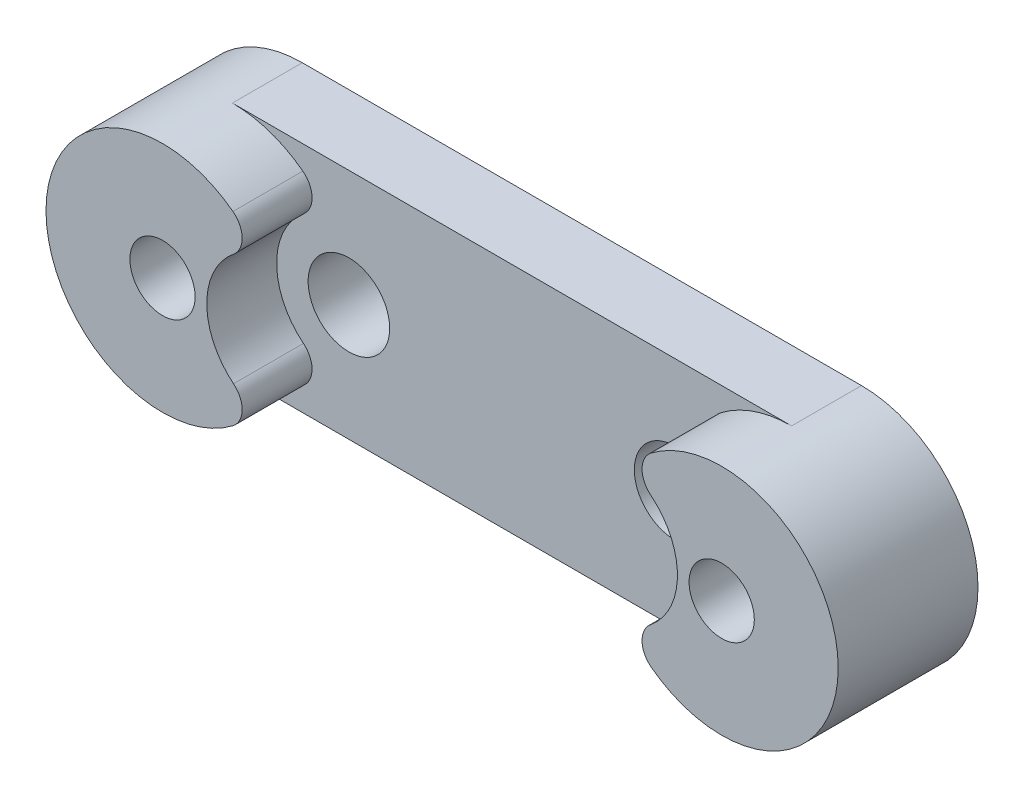
SolidWorks part; units mm, degrees
ref_plane "Front Plane" through (0, 0, 0) normal (0, 0, 1) x (1, 0, 0)
ref_plane "Top Plane" through (0, 0, 0) normal (0, 1, 0) x (1, 0, 0)
ref_plane "Right Plane" through (0, 0, 0) normal (1, 0, 0) x (0, 0, -1)
sketch "Sketch1" plane through (0, 0, 0) normal (0, 0, 1) x (1, 0, 0)
  line L0 (0, 19.1439) -> (0, 0) construction
  line L1 (0, 0) -> (-7, 0) construction
  line L2 (-12, 0) -> (12, 0) construction
  line L3 (-12, 5) -> (12, 5)
  line L4 (-12, -5) -> (12, -5)
  circle A0 centre (-7, 0) radius 1.75
  circle A1 centre (-12, 0) radius 1.75
  circle A2 centre (12, 0) radius 1.75
  circle A3 centre (7, 0) radius 1.75
  arc A4 (-12, 5) -> (-12, -5) centre (-12, 0) ccw
  arc A5 (12, -5) -> (12, 5) centre (12, 0) ccw
  point P11 (0, 0)
  dimension "D1" = 3.5
  dimension "D2" = 3.5
  dimension "D3" = 24
  dimension "D4" = 14
  dimension "D5" = 5
extrude "Boss-Extrude1" add sketch "Sketch1" along normal blind 3
sketch "Sketch2" plane through (0, 0, 3) normal (0, 0, 1) x (1, 0, 0)
  line L0 (0, 0) -> (0, 11.704) construction
  arc A0 (-7.961, 2.9473) -> (-7.961, -2.9473) centre (-12, 0) ccw
  arc A1 (-7.961, 2.9473) -> (-7.961, -2.9473) centre (-7, 0) ccw
  arc A2 (-12, 5) -> (-12, -5) centre (-12, 0) ccw construction
  arc A3 (7.961, 2.9473) -> (7.961, -2.9473) centre (7, 0) cw
  arc A4 (7.961, 2.9473) -> (7.961, -2.9473) centre (12, 0) cw
  circle A5 centre (-12, 0) radius 1.4
  circle A6 centre (12, 0) radius 1.4
  dimension "D1" = 6.2
  dimension "D2" = 2.8
  dimension "D3" = 2.8
extrude "Boss-Extrude2" add sketch "Sketch2" along normal blind 3 and the other way blind 3
fillet "Fillet1" radius 1 4 edges at (7.961, 2.9473, 4.5) (7.961, -2.9473, 4.5) (-7.961, -2.9473, 4.5) (-7.961, 2.9473, 4.5)
